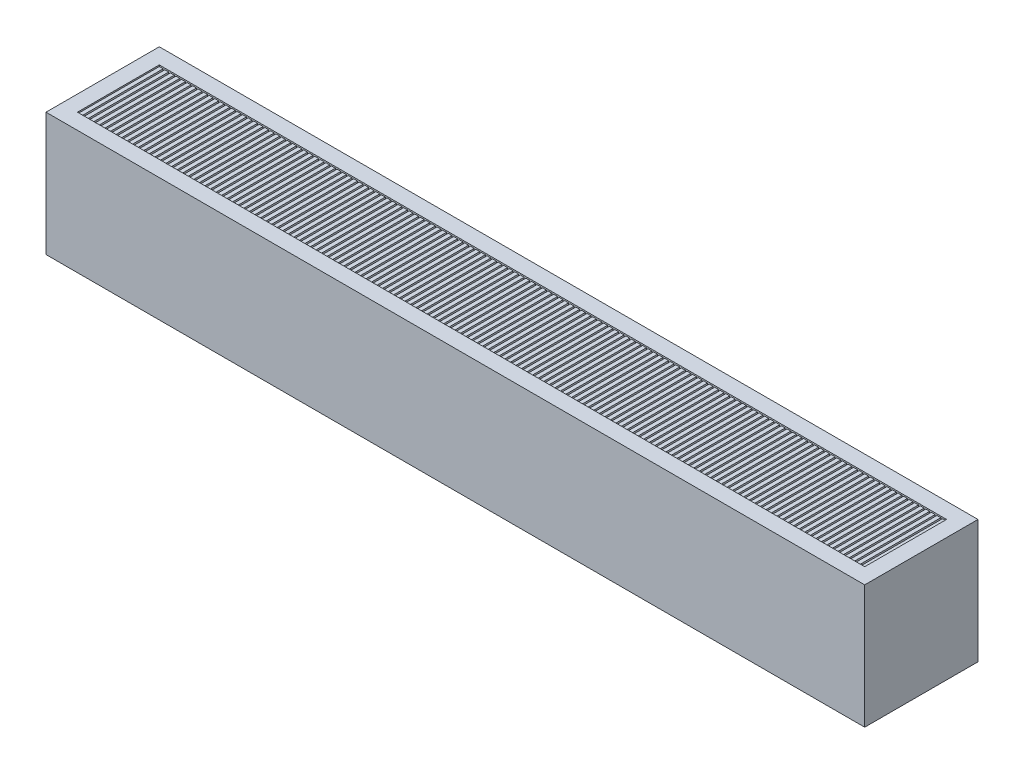
SolidWorks part; units mm, degrees
ref_plane "Front Plane" through (0, 0, 0) normal (0, 0, 1) x (1, 0, 0)
ref_plane "Top Plane" through (0, 0, 0) normal (0, 1, 0) x (1, 0, 0)
ref_plane "Right Plane" through (0, 0, 0) normal (1, 0, 0) x (0, 0, -1)
sketch "Sketch1" plane through (0, 0, 0) normal (0, 1, 0) x (1, 0, 0)
  line L0 (0, 0) -> (737, 0)
  line L1 (737, 0) -> (737, 102)
  line L2 (737, 102) -> (0, 102)
  line L3 (0, 102) -> (0, 0)
  dimension "D1" = 737
  dimension "D2" = 102
extrude "Boss-Extrude1" add sketch "Sketch1" along normal blind 111 contours L3 L0 L1 L2
sketch "Sketch2" plane through (0, 111, 0) normal (0, 1, 0) x (1, 0, 0)
  line L2 (14.1421, 87.8579) -> (14.1421, 14.1421)
  line L3 (0, 0) -> (737, 0) construction
  line L4 (368.5, 102) -> (368.5, 0) construction
  line L5 (737, 102) -> (0, 102) construction
  line L7 (722.8579, 87.8579) -> (722.8579, 14.1421)
  line L9 (14.1421, 87.8579) -> (722.8579, 87.8579)
  line L10 (14.1421, 14.1421) -> (722.8579, 14.1421)
  line L11 (0, 102) -> (0, 0)
  line L12 (737, 102) -> (737, 0)
extrude "Cut-Extrude1" cut sketch "Sketch2" against normal blind 12 contours L4 L9 L2 L10 | L9 L4 L10 L7 region at (191.3211, 111, -51) region at (545.6789, 111, -51)
sketch "Sketch10" plane through (0, 0, -87.8579) normal (0, 0, 1) x (1, 0, 0)
  line L0 (14.1421, 99) -> (14.1421, 109.7173)
  line L2 (14.1421, 109.7173) -> (17.6106, 109.7173)
  line L3 (17.6106, 109.7173) -> (17.6106, 99)
  line L4 (14.1421, 99) -> (722.8579, 99) construction
  line L5 (14.1421, 99) -> (17.6106, 99)
  point P1 (17.6106, 99)
extrude "Boss-Extrude3" add sketch "Sketch10" along normal blind 74
pattern_linear "LPattern1" count 142 spacing 5 along (1, 0, 0) of "Boss-Extrude3"
